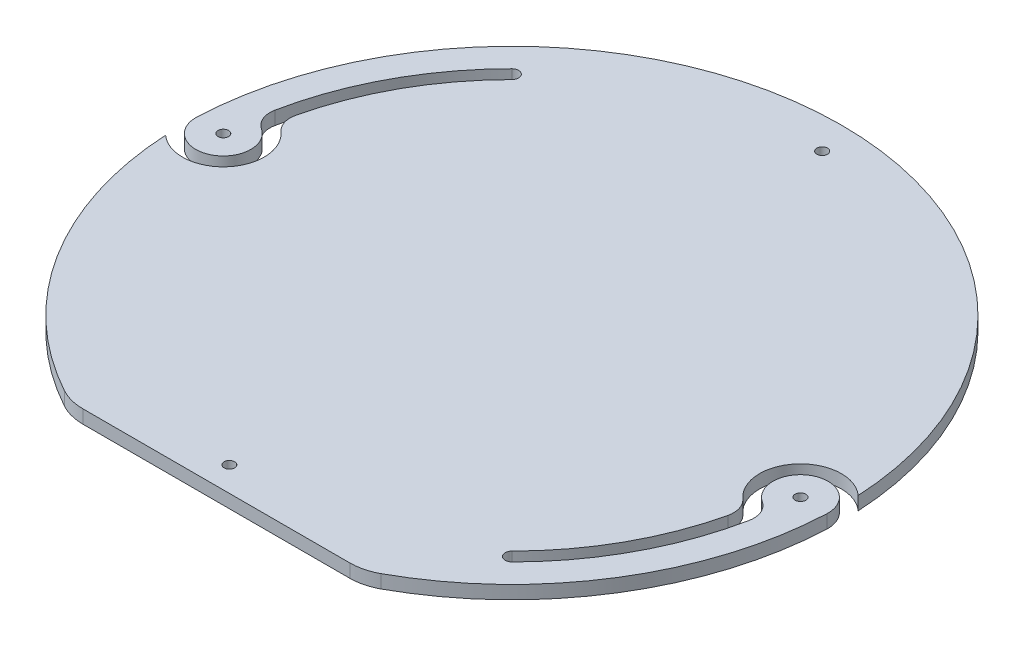
SolidWorks part; units mm, degrees
material "ABS"
ref_plane "Front Plane" through (0, 0, 0) normal (0, 0, 1) x (1, 0, 0)
ref_plane "Top Plane" through (0, 0, 0) normal (0, 1, 0) x (1, 0, 0)
ref_plane "Right Plane" through (0, 0, 0) normal (1, 0, 0) x (0, 0, -1)
sketch "Sketch1" plane through (0, 0, 0) normal (0, 1, 0) x (1, 0, 0)
  line L0 (-30.03, -64.8129) -> (30.03, -64.8129) construction
  line L1 (0, -85) -> (0, 0) construction
  line L2 (0, -85) -> (32.4891, -64.8129) construction
  line L3 (-30.03, -66.5129) -> (30.03, -66.5129)
  arc A0 (34.8348, -63.5829) -> (-34.8348, -63.5829) centre (0, 0) ccw construction
  circle A1 centre (0, -85) radius 38.25 construction
  arc A2 (30.03, -64.8129) -> (34.8348, -63.5829) centre (30.03, -54.8129) ccw construction
  arc A3 (-30.03, -64.8129) -> (-34.8348, -63.5829) centre (-30.03, -54.8129) cw construction
  arc A4 (35.6516, -65.0738) -> (-35.6516, -65.0738) centre (0, 0) ccw
  arc A5 (-30.03, -66.5129) -> (-35.6516, -65.0738) centre (-30.03, -54.8129) cw
  arc A6 (30.03, -66.5129) -> (35.6516, -65.0738) centre (30.03, -54.8129) ccw
  dimension "D1" = 145
  dimension "D2" = 76.5
  dimension "D4" = 10
  dimension "D3" = 85
  dimension "D5" = 1.7
extrude "Boss-Extrude1" add sketch "Sketch1" along normal blind 3
sketch "Sketch2" plane through (0, 3, 0) normal (0, 1, 0) x (1, 0, 0)
  line L0 (0, 0) -> (2.9225, 66.9362) construction
  line L1 (0, 0) -> (-2.6608, -60.9419) construction
  line L2 (0, 0) -> (-67.9353, 2.9661) construction
  line L3 (0, 0) -> (67.9353, -2.9661) construction
  line L4 (0, 0) -> (0, -66.5129) construction
  line L5 (-30.03, -66.5129) -> (30.03, -66.5129) construction
  circle A0 centre (-2.6608, -60.9419) radius 1.2
  circle A1 centre (-67.9353, 2.9661) radius 1.2
  circle A2 centre (2.9225, 66.9362) radius 1.2
  circle A3 centre (67.9353, -2.9661) radius 1.2
  dimension "D4" = 2.4
  dimension "D1" = 67
  dimension "D2" = 61
  dimension "D3" = 2.5
  dimension "D5" = 68
extrude "Cut-Extrude1" cut sketch "Sketch2" against normal through all
sketch "Sketch3" plane through (0, 3, 0) normal (0, 1, 0) x (1, 0, 0)
  line L0 (-48.0833, 48.0833) -> (-45.9619, 45.9619) construction
  line L1 (0, 0) -> (-74.2, 0) construction
  line L2 (-61.7353, 2.9661) -> (-58.7353, 2.9661) construction
  line L3 (48.0833, -48.0833) -> (45.9619, -45.9619) construction
  line L4 (0, 0) -> (74.2, 0) construction
  line L5 (61.7353, -2.9661) -> (58.7353, -2.9661) construction
  arc A0 (-74.1294, 3.2366) -> (-64.5294, 8.1468) centre (-67.9353, 2.9661) ccw
  arc A1 (35.6516, -65.0738) -> (-35.6516, -65.0738) centre (0, 0) ccw construction
  arc A2 (-66.6861, 13.303) -> (-48.0833, 48.0833) centre (0, 0) cw
  arc A3 (-45.9619, 45.9619) -> (-63.3242, 14.6643) centre (0, 0) ccw
  arc A4 (-61.7919, 9.8144) -> (-74.0993, -3.8635) centre (-67.9353, 2.9661) cw
  arc A5 (-74.0993, -3.8635) -> (-74.1294, 3.2366) centre (0, 0) cw
  arc A6 (-45.9619, 45.9619) -> (-48.0833, 48.0833) centre (-47.0226, 47.0226) ccw
  arc A7 (-63.3242, 14.6643) -> (-61.7919, 9.8144) centre (-58.4531, 13.5363) ccw
  arc A8 (-64.5294, 8.1468) -> (-66.6861, 13.303) centre (-61.7827, 12.3248) cw
  arc A9 (74.1294, -3.2366) -> (64.5294, -8.1468) centre (67.9353, -2.9661) ccw
  arc A10 (66.6861, -13.303) -> (48.0833, -48.0833) centre (0, 0) cw
  arc A11 (45.9619, -45.9619) -> (63.3242, -14.6643) centre (0, 0) ccw
  arc A12 (61.7919, -9.8144) -> (74.0993, 3.8635) centre (67.9353, -2.9661) cw
  arc A13 (74.0993, 3.8635) -> (74.1294, -3.2366) centre (0, 0) cw
  arc A14 (45.9619, -45.9619) -> (48.0833, -48.0833) centre (47.0226, -47.0226) ccw
  arc A15 (63.3242, -14.6643) -> (61.7919, -9.8144) centre (58.4531, -13.5363) ccw
  arc A16 (64.5294, -8.1468) -> (66.6861, -13.303) centre (61.7827, -12.3248) cw
  point P39 (0, 0)
  dimension "D3" = 5
  dimension "D1" = 3
  dimension "D2" = 45
  dimension "D4" = 2
extrude "Cut-Extrude2" cut sketch "Sketch3" against normal through all
equation "\"smallPulleyTeeth\"= 30"
equation "\"largePulleyTeeth\"= 30"
equation "\"eighthThick\"= 3.0mm"
equation "\"sixteenthThick\" = 1.7mm"
equation "\"quarterThick\"=6.0mm"
equation "\"OD\" = 145mm"
equation "\"puckAngle\" = 60.5deg"
equation "\"puckDiam\" = 76.5mm"
equation "\"axlePress\" = 5.9mm"
equation "\"press\" = 0.2mm"
equation "\"wheelClear\" = 0.3mm"
equation "\"10-32clear\" = 4.8mm"
equation "\"6-32clear\" = 3.3mm"
equation "\"8-32clear\" = 4.0mm"
equation "\"4-40clear\" = 3.0mm"
equation "\"wheelHeight\" = 22mm"
equation "\"wheelWell\" = 65mm"
equation "\"D1@Sketch1\"=\"OD\""
equation "\"D1@Boss-Extrude1\"=\"eighthThick\""
equation "\"D2@Sketch1\"=\"puckDiam\""
equation "\"puckDist\" = 85mm"
equation "\"scoopFillet\" = 5mm"
equation "\"10-32tap\" = 4.45mm"
equation "\"ledSmall\" = 3.1mm"
equation "\"ledLarge\" = 4.2mm"
equation "\"ledLength\" = 4.2mm"
equation "\"D3@Sketch1\"=\"puckDist\""
equation "\"D5@Sketch1\"=\"sixteenthThick\""
